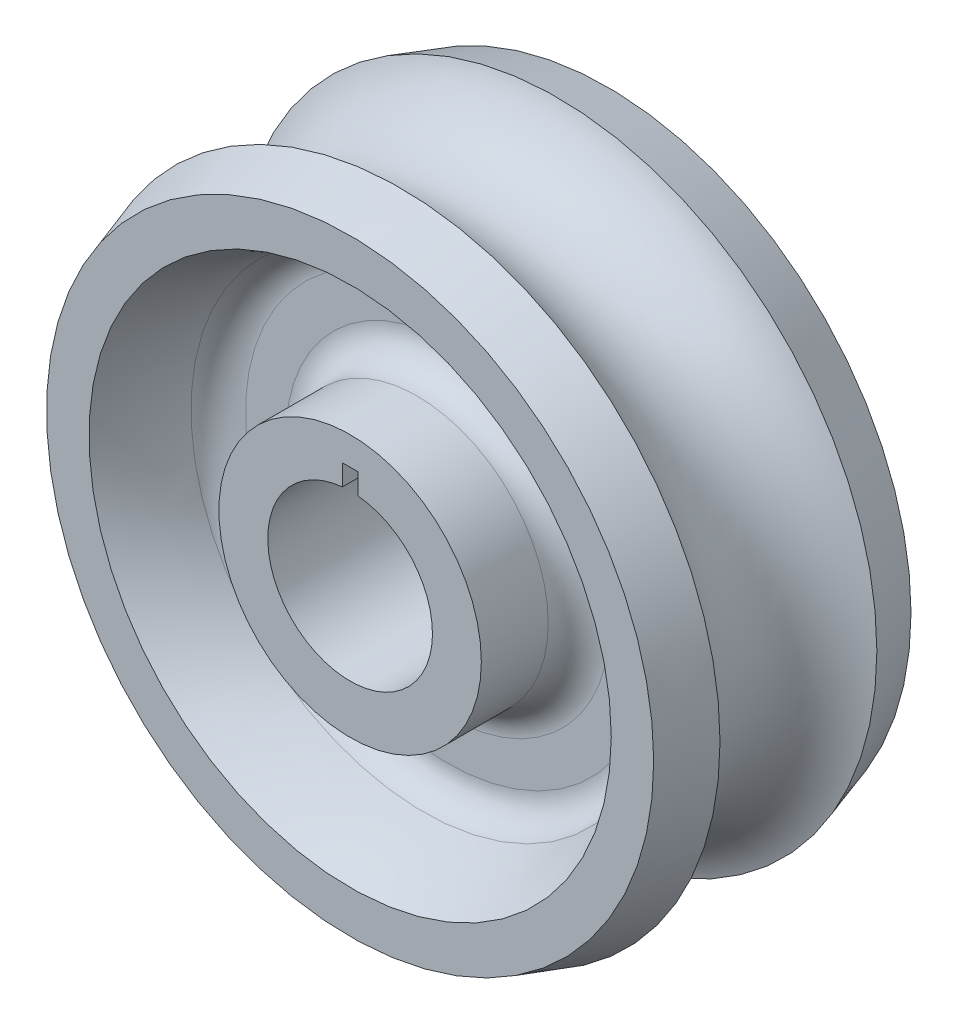
SolidWorks part; units mm, degrees
material "PW20:29:Sc:0:"
ref_plane "Front" through (0, 0, 0) normal (0, 0, 1) x (1, 0, 0)
ref_plane "Top" through (0, 0, 0) normal (0, 1, 0) x (1, 0, 0)
ref_plane "Right" through (0, 0, 0) normal (1, 0, 0) x (0, 0, -1)
other "Configuration Table"
sketch "Sketch1" plane through (0, 0, 0) normal (1, 0, 0) x (0, 0, -1)
  line L0 (0, 0) -> (159.8623, 0) construction
  line L1 (0, 0) -> (0, 93.2897) construction
  line L2 (-12.5, 8) -> (12.5, 8)
  line L3 (12.5, 8) -> (12.5, 12.75)
  line L4 (12.5, 12.75) -> (6, 12.75)
  line L5 (3, 15.75) -> (3, 19.676)
  line L6 (12.5, 25.375) -> (12.5, 29.5)
  line L7 (12.5, 29.5) -> (7.6194, 31.0618)
  line L8 (-12.5, 29.5) -> (-7.6194, 31.0618)
  line L9 (-12.5, 25.375) -> (-12.5, 29.5)
  line L10 (-3, 15.75) -> (-3, 19.676)
  line L11 (-12.5, 12.75) -> (-6, 12.75)
  line L12 (-12.5, 8) -> (-12.5, 12.75)
  arc A0 (6, 12.75) -> (3, 15.75) centre (6, 15.75) cw
  arc A1 (3, 19.676) -> (5.3571, 22.6064) centre (6, 19.676) cw
  arc A2 (5.3571, 22.6064) -> (12.5, 25.375) centre (0, 47.0256) ccw
  arc A3 (7.6194, 31.0618) -> (-7.6194, 31.0618) centre (0, 33.5) cw
  arc A4 (-5.3571, 22.6064) -> (-12.5, 25.375) centre (0, 47.0256) cw
  arc A5 (-3, 19.676) -> (-5.3571, 22.6064) centre (-6, 19.676) ccw
  arc A6 (-6, 12.75) -> (-3, 15.75) centre (-6, 15.75) ccw
  point P29 (0, 8)
  dimension "D1" = 25
  dimension "D2" = 3
  dimension "D4" = 8
  dimension "D9" = 25
  dimension "D3" = 50.75
  dimension "D5" = 6
  dimension "D6" = 4.75
  dimension "D7" = 16
  dimension "D8" = 21.5
  dimension "D10" = 67
revolve "Base-Revolve" add sketch "Sketch1" angle 360 about L0
sketch "Sketch2" plane through (0, 0, 12.5) normal (0, 0, 1) x (1, 0, 0)
  line L0 (0, 0) -> (0, 10.5711) construction
  line L1 (-0.75, 7.9648) -> (-0.75, 10)
  line L2 (0.75, 7.9648) -> (0.75, 10)
  line L3 (-0.75, 10) -> (0.75, 10)
  circle A0 centre (0, 0) radius 8 construction
  arc A1 (0.75, 7.9648) -> (-0.75, 7.9648) centre (0, 0) ccw
  dimension "D1" = 1.5
  dimension "D2" = 10
extrude "Cut-Extrude1" cut sketch "Sketch2" against normal through all
ref_axis "Worm CL" through (0, 0, 50) along (0, 0, -1)
